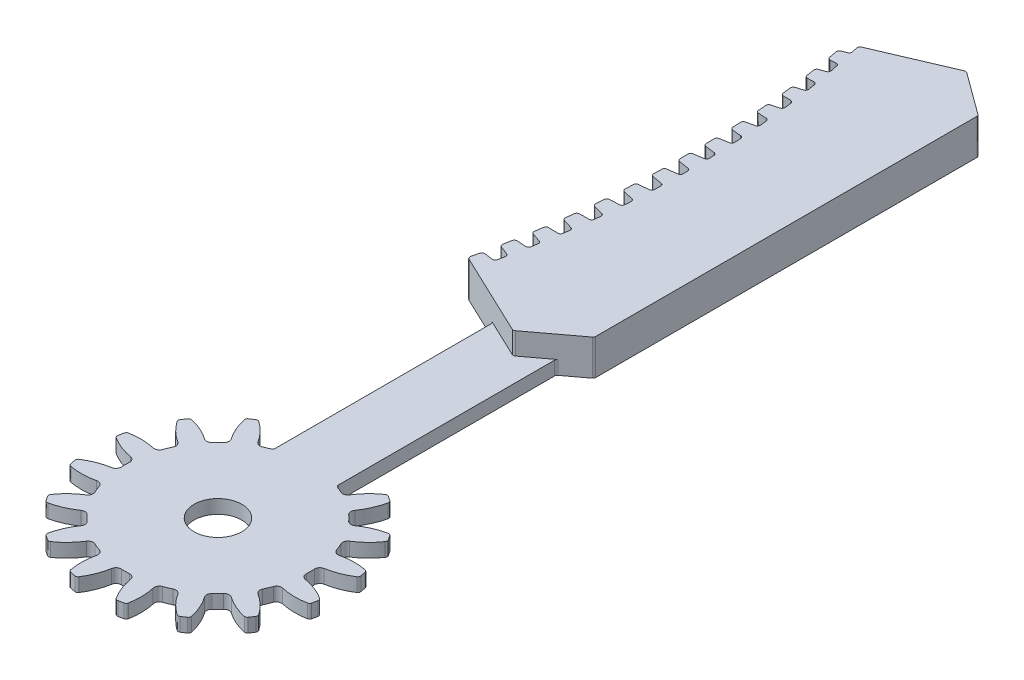
SolidWorks part; units mm, degrees
ref_plane "Front Plane" through (0, 0, 0) normal (0, 0, 1) x (1, 0, 0)
ref_plane "Top Plane" through (0, 0, 0) normal (0, 1, 0) x (1, 0, 0)
ref_plane "Right Plane" through (0, 0, 0) normal (1, 0, 0) x (0, 0, -1)
sketch "Sketch1" plane through (0, 0, 0) normal (0, 1, 0) x (1, 0, 0)
  circle A0 centre (0, 0) radius 22.5
  circle A1 centre (0, 0) radius 4.35
  dimension "D1" = 45
  dimension "D2" = 8.7
extrude "Boss-Extrude1" add sketch "Sketch1" along normal blind 2.5
sketch "Sketch3" plane through (0, 2.5, 0) normal (0, 1, 0) x (1, 0, 0)
  line L0 (0, -1.375) -> (0, 1.375) construction
  line L1 (0, 0) -> (-1.6059, 16.7984) construction
  line L2 (0, 13.4609) -> (-4.1306, 24.8095) construction
  arc A0 (2.3332, 19.8634) -> (-2.3332, 19.8634) centre (0, 0) ccw construction
  arc A1 (1.6059, 16.7984) -> (-1.6059, 16.7984) centre (0, 0) ccw
  circle A2 centre (0, 0) radius 22.5 construction
  arc A3 (-3.577, 22.2139) -> (-1.6059, 16.7984) centre (-13.032, 15.7061) cw
  arc A4 (3.577, 22.2139) -> (1.6059, 16.7984) centre (13.032, 15.7061) ccw
  arc A5 (-3.577, 22.2139) -> (3.577, 22.2139) centre (0, 0) cw
  point P27 (-2.246, 19.6318)
  dimension "D1" = 40
  dimension "D2" = 5.625
  dimension "D3" = 20
  dimension "D4" = 4.677
extrude "Cut-Extrude2" cut sketch "Sketch3" against normal through all
fillet "Fillet1" radius 0.95 2 edges at (-1.6059, 1.25, -16.7984) (1.6059, 1.25, -16.7984)
fillet "Fillet2" radius 0.5 2 edges at (3.577, 1.25, -22.2139) (-3.577, 1.25, -22.2139)
pattern_circular "CirPattern1" count 16 over 360 about axis through (0, 2.5, 0) along (0, 1, 0) of "Cut-Extrude2", "Fillet1", "Fillet2"
sketch "Sketch4" plane through (0, 0, 0) normal (0, 1, 0) x (1, 0, 0)
  line L0 (-5.7669, 15.859) -> (-5.7669, 55.859)
  line L1 (5.7669, 15.859) -> (5.7669, 55.859)
  line L2 (-12.0914, 58.859) -> (-5.7669, 55.859)
  line L3 (5.7669, 55.859) -> (9.7669, 58.859)
  line L4 (9.7669, 58.859) -> (9.7669, 128.859)
  line L5 (9.7669, 128.859) -> (1.697, 134.7648)
  line L6 (1.697, 134.7648) -> (-12.0914, 128.859)
  line L8 (-5.7669, 15.859) -> (5.7669, 15.859)
  line L9 (-5.7669, 55.859) -> (1.2984, 52.5077)
  line L10 (1.2984, 52.5077) -> (5.7669, 55.859)
  arc A0 (-12.0914, 128.859) -> (-12.0914, 58.859) centre (-157.9509, 93.859) cw
  point P31 (-7.9509, 93.859)
  point P32 (9.7669, 93.859)
  dimension "D2" = 70
  dimension "D3" = 150
  dimension "D1" = 40
  dimension "D4" = 7
  dimension "D5" = 70
  dimension "D6" = 5
  dimension "D7" = 15
  dimension "D8" = 10
  dimension "D9" = 3
extrude "Boss-Extrude3" add sketch "Sketch4" along normal up to surface (2.5 mm away) contours L10 L9 L0 L8 L1 region at (-0.0189, 0, -35.0334) up to face at (0, 2.5, 4.35)
extrude "Boss-Extrude4" add sketch "Sketch4<3>" along normal blind 6.5 contours L6 A0 L2 L9 L10 L3 L4 L5 region at (0.1401, 0, -93.7296)
sketch "Sketch4<3>" plane through (0, 0, 0) normal (0, 1, 0) x (1, 0, 0) same geometry as "Sketch4"
fillet "Fillet5" radius 0.5 8 edges at (1.697, 3.25, -134.7648) (9.7669, 3.25, -128.859) (5.7669, 1.25, -55.859) (9.7669, 3.25, -58.859) (5.7669, 1.25, -15.859) (-5.7669, 1.25, -15.859) (-5.7669, 1.25, -55.859) (1.2984, 4.5, -52.5077)
sketch "Sketch6" plane through (0, 0, 0) normal (0, 1, 0) x (1, 0, 0)
  line L0 (-12.0914, 128.859) -> (-14.3895, 127.8747)
  line L1 (-14.3502, 59.9305) -> (-12.0914, 58.859)
  line L2 (1.435, 134.6525) -> (-12.0914, 128.859) construction
  line L3 (-12.0914, 58.859) -> (1.0256, 52.6371) construction
  line L6 (-1010.6112, 95.5891) -> (48989.3888, 95.5891) construction
  line L8 (-10.3916, 124.268) -> (-12.9258, 124.1075)
  line L10 (-13.3401, 126.3735) -> (-10.9795, 127.3092)
  line L12 (-9.5593, 119.2262) -> (-12.142, 119.1648)
  line L14 (-12.483, 121.4429) -> (-10.0456, 122.2995)
  line L16 (-8.8992, 114.1587) -> (-11.5182, 114.1993)
  line L18 (-11.7854, 116.4873) -> (-9.282, 117.258)
  line L20 (-8.4121, 109.0718) -> (-11.055, 109.2163)
  line L22 (-11.2482, 111.5117) -> (-8.69, 112.191)
  line L24 (-8.0985, 103.9717) -> (-10.7529, 104.2209)
  line L26 (-10.8719, 106.5213) -> (-8.2705, 107.1046)
  line L28 (-7.9589, 98.8646) -> (-10.6122, 99.2183)
  line L29 (-7.9873, 97.1598) -> (-10.6287, 96.7407)
  line L30 (-10.6569, 101.5215) -> (-8.0242, 102.005)
  line L31 (-10.6023, 94.4373) -> (-7.951, 94.0181)
  line L33 (-7.9589, 92.3135) -> (-10.6122, 91.9598)
  line L35 (-10.6569, 89.6567) -> (-8.0242, 89.1732)
  line L37 (-8.0985, 87.2065) -> (-10.7529, 86.9573)
  line L39 (-10.8719, 84.6568) -> (-8.2705, 84.0736)
  line L41 (-8.4121, 82.1063) -> (-11.055, 81.9619)
  line L43 (-11.2482, 79.6665) -> (-8.69, 78.9871)
  line L44 (-8.8992, 77.0194) -> (-11.5182, 76.9789)
  line L45 (-11.7854, 74.6909) -> (-9.282, 73.9201)
  line L46 (-9.5593, 71.952) -> (-12.142, 72.0134)
  line L47 (-12.483, 69.7352) -> (-10.0456, 68.8787)
  line L49 (-10.3916, 66.9102) -> (-12.9258, 67.0706)
  line L51 (-13.3401, 64.8047) -> (-10.9795, 63.8689)
  line L53 (-11.4145, 61.8111) -> (-13.8743, 62.1295)
  arc A0 (-14.3895, 127.8747) -> (-13.9, 125.6238) centre (-165.6011, 93.8151) cw
  arc A1 (-12.0914, 58.859) -> (-11.4145, 61.8111) centre (-157.9509, 93.859) ccw
  arc A2 (-12.0914, 58.859) -> (-12.0914, 128.859) centre (-157.9509, 93.859) ccw construction
  arc A3 (-13.8743, 62.1295) -> (-14.3502, 59.9305) centre (-165.6011, 93.8151) cw
  arc A4 (-12.9258, 67.0706) -> (-13.3401, 64.8047) centre (-165.6011, 93.8151) cw
  arc A5 (-10.9795, 63.8689) -> (-10.3916, 66.9102) centre (-157.9509, 93.859) ccw
  arc A6 (-10.0456, 68.8787) -> (-9.5593, 71.952) centre (-157.9509, 93.859) ccw
  arc A7 (-12.142, 72.0134) -> (-12.483, 69.7352) centre (-165.6011, 93.8151) cw
  arc A8 (-9.282, 73.9201) -> (-8.8992, 77.0194) centre (-157.9509, 93.859) ccw
  arc A9 (-11.5182, 76.9789) -> (-11.7854, 74.6909) centre (-165.6011, 93.8151) cw
  arc A10 (-8.69, 78.9871) -> (-8.4121, 82.1063) centre (-157.9509, 93.859) ccw
  arc A11 (-11.055, 81.9619) -> (-11.2482, 79.6665) centre (-165.6011, 93.8151) cw
  arc A12 (-8.2705, 84.0736) -> (-8.0985, 87.2065) centre (-157.9509, 93.859) ccw
  arc A13 (-10.7529, 86.9573) -> (-10.8719, 84.6568) centre (-165.6011, 93.8151) cw
  arc A14 (-8.0242, 89.1732) -> (-7.9589, 92.3135) centre (-157.9509, 93.859) ccw
  arc A15 (-10.6122, 91.9598) -> (-10.6569, 89.6567) centre (-165.6011, 93.8151) cw
  arc A16 (-7.951, 94.0181) -> (-7.9873, 97.1598) centre (-157.9509, 93.859) ccw
  arc A17 (-10.6287, 96.7407) -> (-10.6023, 94.4373) centre (-165.6011, 93.8151) cw
  arc A30 (-11.4022, 125.8505) -> (-12.0914, 128.859) centre (-157.9509, 93.859) ccw
  arc A31 (-12.9258, 124.1075) -> (-13.3401, 126.3735) centre (-165.6011, 97.3631) ccw
  arc A32 (-10.9795, 127.3092) -> (-10.3916, 124.268) centre (-157.9509, 97.3191) cw
  arc A33 (-12.142, 119.1648) -> (-12.483, 121.4429) centre (-165.6011, 97.3631) ccw
  arc A34 (-10.0456, 122.2995) -> (-9.5593, 119.2262) centre (-157.9509, 97.3191) cw
  arc A35 (-11.5182, 114.1993) -> (-11.7854, 116.4873) centre (-165.6011, 97.3631) ccw
  arc A36 (-9.282, 117.258) -> (-8.8992, 114.1587) centre (-157.9509, 97.3191) cw
  arc A37 (-11.055, 109.2163) -> (-11.2482, 111.5117) centre (-165.6011, 97.3631) ccw
  arc A38 (-8.69, 112.191) -> (-8.4121, 109.0718) centre (-157.9509, 97.3191) cw
  arc A39 (-10.7529, 104.2209) -> (-10.8719, 106.5213) centre (-165.6011, 97.3631) ccw
  arc A40 (-8.2705, 107.1046) -> (-8.0985, 103.9717) centre (-157.9509, 97.3191) cw
  arc A41 (-10.6122, 99.2183) -> (-10.6569, 101.5215) centre (-165.6011, 97.3631) ccw
  arc A42 (-8.0242, 102.005) -> (-7.9589, 98.8646) centre (-157.9509, 97.3191) cw
  point P77 (-12.3083, 70.8737)
  point P78 (-11.6475, 75.8344)
  point P79 (-11.1473, 80.8138)
  point P80 (-10.8081, 85.8068)
  point P81 (-10.6302, 90.8082)
  point P82 (-10.6112, 95.5891)
  point P83 (-7.9609, 95.5891)
  point P84 (-13.1288, 65.9369)
  point P85 (-14.1082, 61.0291)
  dimension "D3" = 155
  dimension "D1" = 2.5
  dimension "D2" = 2.5
  dimension "D11" = 18
  dimension "D12" = 18
  dimension "D13" = 18
  dimension "D14" = 18
  dimension "D15" = 18
  dimension "D16" = 18
  dimension "D17" = 18
  dimension "D18" = 18
  dimension "D20" = 2.25
  dimension "D19" = 1.85
  dimension "D21" = 1.85
  dimension "D22" = 1.85
  dimension "D23" = 1.85
  dimension "D24" = 1.85
  dimension "D25" = 1.85
extrude "Boss-Extrude5" add sketch "Sketch6" along normal up to surface (6.5 mm away) contours A32 L10 A31 L8 | A34 L14 A33 L12 | A36 L18 A35 L16 | A38 L22 A37 L20 | A40 L26 A39 L24 | A42 L30 A41 L28 | L33 A15 L35 A14 | L41 A11 L43 A10 | L44 A9 L45 A8 | L46 A7 L47 A6 | L51 A5 L49 A4 | L53 A3 L1 A1 | L31 A16 L29 A17 | L39 A12 L37 A13 region at (-12.87, 0, -60.667) region at (-11.8447, 0, -125.5266) region at (-10.9906, 0, -120.5436) region at (-10.3023, 0, -115.5341) region at (-9.7809, 0, -110.5038) region at (-9.427, 0, -105.4585) region at (-9.241, 0, -100.4038) region at (-9.241, 0, -90.7744) region at (-9.7809, 0, -80.6744) region at (-10.3023, 0, -75.6441) region at (-10.9906, 0, -70.6346) region at (-11.8447, 0, -65.6516) up to face at (2.4658, 6.5, -93.772)
fillet "Fillet6" radius 0.5 56 edges at (-12.0914, 3.25, -128.859) (-12.483, 3.25, -121.4429) (-11.6662, 3.25, -127.037) (-13.3401, 3.25, -126.3735) (-12.9258, 3.25, -124.1075) (-11.0569, 3.25, -124.2259) (-10.6322, 3.25, -122.0933) (-12.142, 3.25, -119.1648) (-10.1092, 3.25, -119.2131) (-9.7639, 3.25, -117.1097) (-11.7854, 3.25, -116.4873) (-11.5182, 3.25, -114.1993) (-9.3318, 3.25, -114.1654) (-9.0632, 3.25, -112.0919) (-11.2482, 3.25, -111.5117) (-11.055, 3.25, -109.2163) (-8.7261, 3.25, -109.089) (-8.5317, 3.25, -107.046) (-10.8719, 3.25, -106.5213) (-10.7529, 3.25, -104.2209) (-8.2935, 3.25, -103.99) (-8.1708, 3.25, -101.978) (-10.6569, 3.25, -101.5215) (-10.6122, 3.25, -99.2183) (-8.0348, 3.25, -98.8747) (-7.9873, 3.25, -97.1598) (-10.6287, 3.25, -96.7407) (-10.6023, 3.25, -94.4373) (-7.951, 3.25, -94.0181) (-7.9589, 3.25, -92.3135) (-10.6122, 3.25, -91.9598) (-10.6569, 3.25, -89.6567) (-8.0242, 3.25, -89.1732) (-8.0985, 3.25, -87.2065) (-10.7529, 3.25, -86.9573) (-10.8719, 3.25, -84.6568) (-8.2705, 3.25, -84.0736) (-8.4121, 3.25, -82.1063) (-11.055, 3.25, -81.9619) (-11.2482, 3.25, -79.6665) (-8.69, 3.25, -78.9871) (-8.8992, 3.25, -77.0194) (-11.5182, 3.25, -76.9789) (-11.7854, 3.25, -74.6909) (-9.282, 3.25, -73.9201) (-9.5593, 3.25, -71.952) (-12.142, 3.25, -72.0134) (-12.483, 3.25, -69.7352) (-10.0456, 3.25, -68.8787) (-10.3916, 3.25, -66.9102) (-12.9258, 3.25, -67.0706) (-13.3401, 3.25, -64.8047) (-10.9795, 3.25, -63.8689) (-11.4145, 3.25, -61.8111) (-13.8743, 3.25, -62.1295) (-14.3502, 3.25, -59.9305)
equation "\"N\"= 16"
equation "\"Module\"= \"outerD\" / ( \"N\" + 2 )"
equation "\"outerD\"= 45"
equation "\"pitchD\"= \"N\" * \"Module\""
equation "\"Backlash\"= 0.3 * \"Module\""
equation "\"ArcLength\"= ( ( \"Module\" * pi ) / 2 ) + \"Backlash\""
equation "\"FilletR\"= 0.38 * \"Module\""
equation "\"D1@Sketch3\"=\"pitchD\""
equation "\"toothdepth\"= 2.25 * \"Module\""
equation "\"D2@Sketch3\"=\"toothdepth\""
equation "\"D3@Sketch3\"=20"
equation "\"D4@Sketch3\"=\"ArcLength\""
equation "\"D1@Fillet1\"=\"FilletR\""
equation "\"D1@CirPattern1\"=\"N\""
equation "\"D21@Sketch6\"=\"D19@Sketch6\""
equation "\"D22@Sketch6\"=\"D19@Sketch6\""
equation "\"D23@Sketch6\"=\"D19@Sketch6\""
equation "\"D24@Sketch6\"=\"D19@Sketch6\""
equation "\"D25@Sketch6\"=\"D19@Sketch6\""
